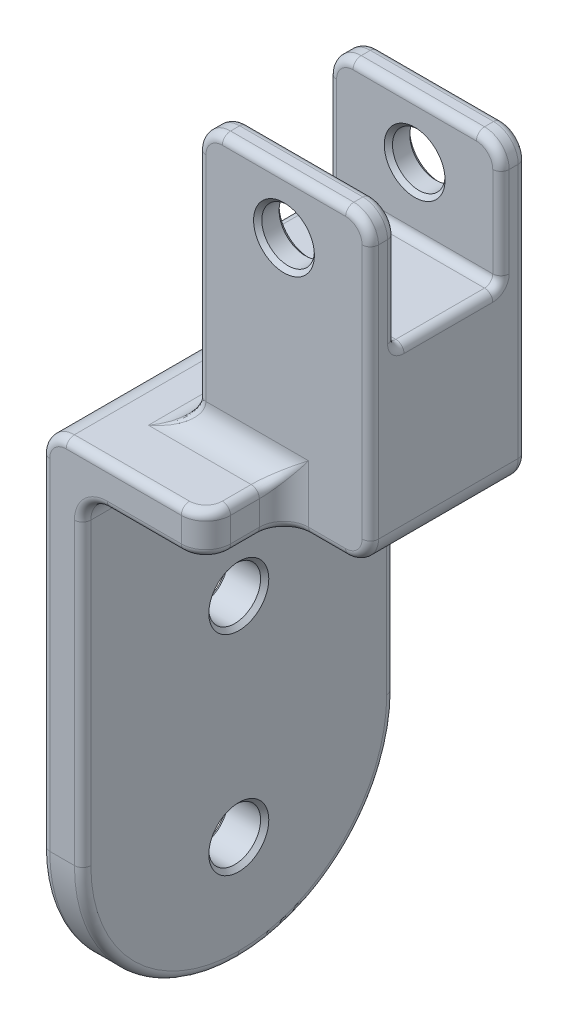
SolidWorks part; units mm, degrees
ref_plane "Front" through (0, 0, 0) normal (0, 0, 1) x (1, 0, 0)
ref_plane "Top" through (0, 0, 0) normal (0, 1, 0) x (1, 0, 0)
ref_plane "Right" through (0, 0, 0) normal (1, 0, 0) x (0, 0, -1)
ref_plane "Plane1" through (39.1342, 0, 0) normal (1, 0, 0) x (0, 0, -1)
sketch "Sketch1" plane through (39.1342, 0, 0) normal (1, 0, 0) x (0, 0, -1)
  line L0 (0, -40.64) -> (0, -117.14) construction
  line L1 (-19, -117.14) -> (19, -117.14)
  line L2 (19, -117.14) -> (19, -58.74)
  line L3 (19, -58.74) -> (-19, -58.74)
  line L4 (-10.6654, -117.14) -> (10.6654, -117.14) construction
  line L5 (10.6654, -117.14) -> (10.6654, -58.74) construction
  line L6 (-10.6654, -58.74) -> (-10.6654, -117.14) construction
  line L7 (10.6654, -22.59) -> (-10.6654, -22.59) construction
  line L8 (-10.6654, -58.74) -> (10.6654, -58.74) construction
  line L9 (10.6654, -58.74) -> (10.6654, -22.59) construction
  line L10 (-10.6654, -22.59) -> (-10.6654, -58.74) construction
  line L11 (-19, -58.74) -> (-19, -117.14)
  circle A3 centre (0, -104.14) radius 3.15
  circle A4 centre (0, -78.74) radius 3.15
  circle A5 centre (0, -40.64) radius 3.45 construction
  point P21 (0, -117.14)
  dimension "D1" = 6.3
  dimension "D2" = 6.3
  dimension "D4" = 25.4
  dimension "D5" = 38.1
  dimension "D3" = 20
  dimension "D6" = 13
  dimension "D7" = 38
extrude "TibiaMount" add sketch "Sketch1" along normal blind 5
sketch "Sketch2" plane through (0, 0, 0) normal (0, 0, 1) x (1, 0, 0)
  line L2 (39.1342, -58.74) -> (39.1342, -117.14) construction
  line L3 (44.1342, -58.74) -> (39.1342, -58.74)
  line L4 (44.1342, -58.74) -> (59.1342, -58.74)
  line L9 (44.1342, -58.74) -> (39.1342, -58.74) construction
  line L10 (44.1342, -58.74) -> (44.1342, -117.14) construction
  line L11 (39.1342, -58.74) -> (39.1342, -117.14) construction
  line L12 (44.1342, -117.14) -> (39.1342, -117.14) construction
  dimension "D1" = 20
extrude "ConnectingBridge" add sketch "Sketch2" along normal up to surface and the other way up to surface thin up to face at (41.6342, -87.94, 19) other way up to face at (41.6342, -87.94, -19) thin type one direction reverse wall 5
sketch "Sketch6" plane through (0, 0, 0) normal (0, 0, 1) x (1, 0, 0)
  line L0 (48.6342, -28.74) -> (59.1342, -28.74) construction
  line L1 (59.1342, -28.74) -> (59.1342, -58.74) construction
  line L2 (59.1342, -58.74) -> (48.6342, -58.74)
  line L3 (48.6342, -28.74) -> (48.6342, -21.74)
  line L4 (48.6342, -21.74) -> (69.6342, -21.74)
  line L5 (48.6342, -28.74) -> (48.6342, -58.74)
  line L6 (69.6342, -21.74) -> (69.6342, -58.74)
  line L7 (39.1342, -53.74) -> (39.1342, -117.14) construction
  line L8 (39.1342, -53.74) -> (39.1342, -117.14) construction
  line L9 (69.6342, -58.74) -> (59.1342, -58.74)
  circle A0 centre (59.1342, -28.74) radius 3.2
  dimension "D1" = 6.4
  dimension "D2" = 10.5
  dimension "D3" = 30
  dimension "D4" = 21
  dimension "D5" = 7
extrude "EndCap-Holder" add sketch "Sketch6" along normal mid plane 19 contours L2 L5 L3 L4 L6 L9 | A0
sketch "Sketch14" plane through (0, 0, 0) normal (0, 0, 1) x (1, 0, 0)
  point P0 (59.1342, -28.74)
  dimension "D1" = 28.74
  dimension "D2" = 59.1342
sketch "Sketch15" plane through (69.6342, 0, 0) normal (1, 0, 0) x (0, 0, -1)
  line L0 (-9.5, -21.74) -> (9.5, -21.74) construction
  line L1 (-6.4, -36.74) -> (6.4, -36.74)
  line L2 (-6.4, -36.74) -> (-6.4, -21.74)
  line L3 (-6.4, -21.74) -> (6.4, -21.74)
  line L4 (6.4, -36.74) -> (6.4, -21.74)
  line L5 (-6.4, -36.74) -> (6.4, -21.74) construction
  line L6 (-6.4, -21.74) -> (6.4, -36.74) construction
  line L7 (0, -29.24) -> (0, 0) construction
  point P0 (0, -29.24)
  dimension "D1" = 12.8
  dimension "D2" = 15
extrude "EndCap-notch" cut sketch "Sketch15" against normal up to next
chamfer "Chamfer0.5" distance 0.5 angle 45 8 edges at (39.1342, -100.99, 0) (44.1342, -100.99, 0) (39.1342, -75.59, 0) (44.1342, -75.59, 0) (62.3342, -28.74, -9.5) (55.9342, -28.74, -6.4) (62.3342, -28.74, 9.5) (62.3342, -28.74, 6.4)
fillet "Fillet-3.0" radius 3 14 edges at (59.1342, -56.24, 19) (59.1342, -56.24, -19) (39.1342, -53.74, 0) (53.8842, -53.74, -9.5) (53.8842, -53.74, 9.5) (48.6342, -53.74, 0) (59.1342, -56.24, 9.5) (59.1342, -56.24, -9.5) (48.6342, -21.74, 7.95) (48.6342, -21.74, -7.95) (69.6342, -21.74, -7.95) (69.6342, -21.74, 7.95) (44.1342, -58.74, 0) (69.6342, -58.74, 0)
fillet "Fillet-19.0" radius 19 2 edges at (41.6342, -117.14, 19) (41.6342, -117.14, -19)
fillet "Fillet-1.0" radius 1 58 edges at (59.1342, -21.74, -6.4) (49.5128, -22.6187, -6.4) (68.7555, -22.6187, -6.4) (48.6342, -30.74, -6.4) (69.6342, -30.74, -6.4) (48.6342, -36.74, 0) (69.6342, -36.74, 0) (48.6342, -30.74, 6.4) (49.5128, -22.6187, 6.4) (69.6342, -30.74, 6.4) (68.7555, -22.6187, 6.4) (47.7555, -52.8613, -10.3787) (48.6342, -37.74, -9.5) (49.5128, -22.6187, -9.5) (59.1342, -21.74, -9.5) (68.7555, -22.6187, -9.5) (69.6342, -40.24, -9.5) (68.7555, -57.8613, -9.5) (64.3842, -58.74, -9.5) (60.0128, -58.74, -10.3787) (59.1342, -58.74, -14.25) (58.2555, -58.74, -18.1213) (47.7555, -52.8613, 10.3787) (48.6342, -37.74, 9.5) (49.5128, -22.6187, 9.5) (59.1342, -21.74, 9.5) (68.7555, -22.6187, 9.5) (69.6342, -40.24, 9.5) (68.7555, -57.8613, 9.5) (64.3842, -58.74, 9.5) (60.0128, -58.74, 10.3787) (59.1342, -58.74, 14.25) (58.2555, -58.74, 18.1213) (51.6342, -58.74, 19) (45.0128, -59.6187, 19) (44.1342, -79.94, 19) (44.1342, -111.575, 13.435) (44.1342, -111.575, -13.435) (44.1342, -79.94, -19) (45.0128, -59.6187, -19) (60.0128, -52.8613, -10.3787) (60.0128, -52.8613, 10.3787) (59.1342, -53.74, 14.25) (58.2555, -53.74, 18.1213) (49.1342, -53.74, 19) (40.0128, -54.6187, 19) (39.1342, -77.44, 19) (39.1342, -111.575, 13.435) (39.1342, -111.575, -13.435) (39.1342, -77.44, -19) (40.0128, -54.6187, -19) (49.1342, -53.74, -19) (58.2555, -53.74, -18.1213) (59.1342, -36.74, -6.4) (59.1342, -36.74, 6.4) (59.1342, -21.74, 6.4) (51.6342, -58.74, -19) (59.1342, -53.74, -14.25)
equation "\"D2@Sketch1\"=\"D1@Sketch1\""
equation "\"D4@Sketch6\"=\"D2@Sketch6\"*2"
